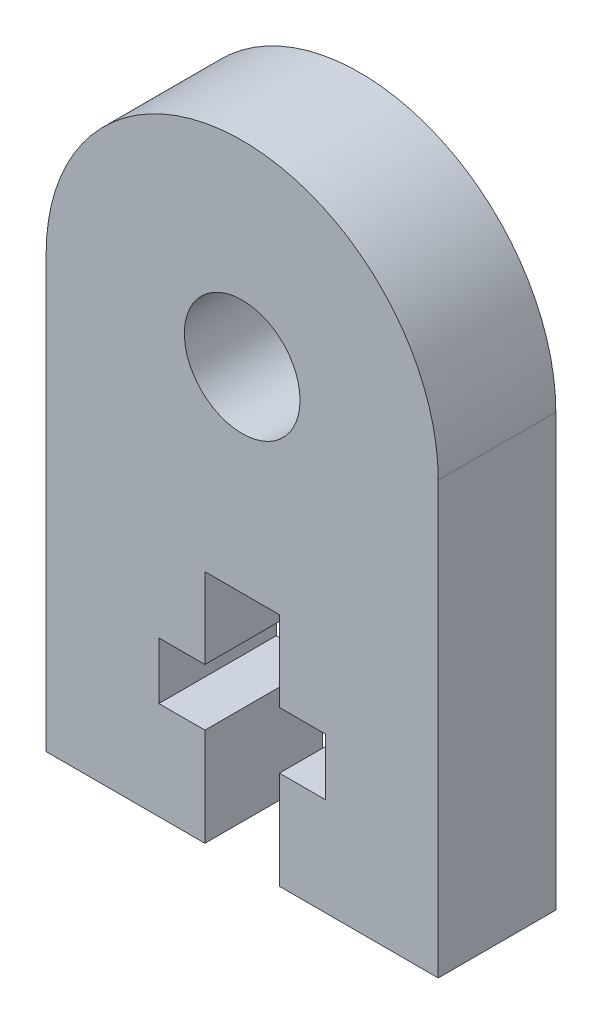
SolidWorks part; units mm, degrees
material "ABS"
ref_plane "Front Plane" through (0, 0, 0) normal (0, 0, 1) x (1, 0, 0)
ref_plane "Top Plane" through (0, 0, 0) normal (0, 1, 0) x (1, 0, 0)
ref_plane "Right Plane" through (0, 0, 0) normal (1, 0, 0) x (0, 0, -1)
sketch "Sketch1" plane through (0, 0, 0) normal (0, 0, 1) x (1, 0, 0)
  line L0 (0, 0) -> (-2.086, 2.086) construction
  line L1 (0, 0) -> (0, 2.95) construction
  line L2 (-10, 0) -> (-10, -22)
  line L3 (-10, -22) -> (10, -22)
  line L4 (10, -22) -> (10, 0)
  line L5 (0, 0) -> (0, -22) construction
  circle A0 centre (0, 0) radius 2.95
  arc A1 (-10, 0) -> (10, 0) centre (0, 0) cw
  dimension "D1" = 5.9
  dimension "D4" = 45
  dimension "D5" = 22
  dimension "D6" = 20
extrude "Boss-Extrude1" add sketch "Sketch1" along normal blind 6
sketch "Sketch3" plane through (0, 0, 6) normal (0, 0, 1) x (1, 0, 0)
  line L0 (-10, -22) -> (10, -22) construction
  line L1 (-1.9, -22) -> (1.9, -22)
  line L2 (-1.9, -22) -> (-1.9, -17)
  line L3 (-1.9, -10) -> (1.9, -10)
  line L4 (1.9, -22) -> (1.9, -17)
  line L5 (0, -10) -> (0, 0) construction
  line L6 (1.9, -14.1) -> (4.25, -14.1)
  line L7 (-4.25, -14.1) -> (-1.9, -14.1)
  line L8 (-4.25, -14.1) -> (-4.25, -17)
  line L9 (-4.25, -17) -> (-1.9, -17)
  line L10 (4.25, -14.1) -> (4.25, -17)
  line L11 (-1.9, -14.1) -> (-1.9, -10)
  line L12 (1.9, -17) -> (4.25, -17)
  line L13 (1.9, -14.1) -> (1.9, -10)
  point P18 (-3.075, -17)
  dimension "D1" = 3.8
  dimension "D3" = 12
  dimension "D4" = 8.5
  dimension "D5" = 2.9
  dimension "D6" = 5
extrude "Cut-Extrude2" cut sketch "Sketch3" against normal through all
equation "\"smallPulleyTeeth\"= 15"
equation "\"largePulleyTeeth\"= 30"
equation "\"eighthThick\"= 2.9mm"
equation "\"sixteenthThick\"= 1.7mm"
equation "\"quarterThick\"=6.0mm"
equation "\"OD\"= 145mm"
equation "\"puckAngle\"= 60.5deg"
equation "\"puckDiam\"= 76.5mm"
equation "\"axlePress\"= 5.9mm"
equation "\"D1@Sketch1\"=\"axlePress\""
equation "\"D1@Boss-Extrude1\"=\"quarterThick\""
equation "\"press\"= 0.2mm"
equation "\"wheelClear\"= 0.3mm"
equation "\"10-32clear\"= 4.8mm"
equation "\"D1@Sketch3\"=\"8-32clear\"-\"press\""
equation "\"6-32clear\"= 3.3mm"
equation "\"8-32clear\"= 4.0mm"
equation "\"wheelHeight\"= 22mm"
equation "\"D5@Sketch1\"=\"wheelHeight\""
equation "\"wheelWell\"= 65mm"
